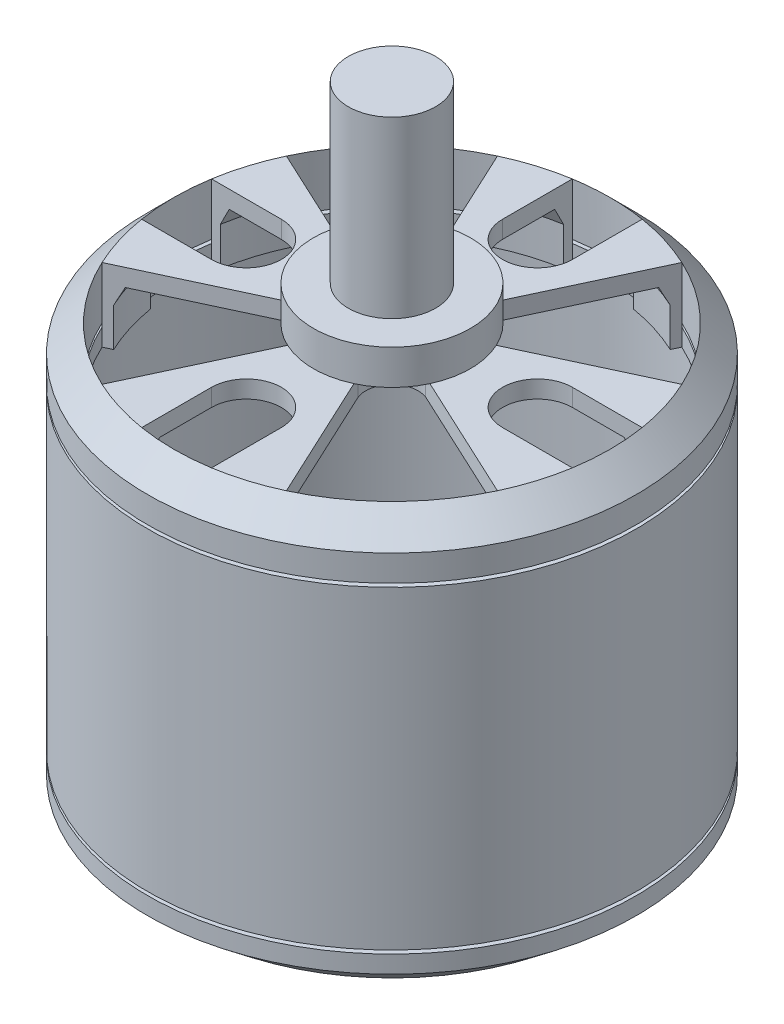
SolidWorks part; units mm, degrees
ref_plane "前视基准面" through (0, 0, 0) normal (0, 0, 1) x (1, 0, 0)
ref_plane "上视基准面" through (0, 0, 0) normal (0, 1, 0) x (1, 0, 0)
ref_plane "右视基准面" through (0, 0, 0) normal (1, 0, 0) x (0, 0, -1)
sketch "草图1" plane through (0, 0, 0) normal (1, 0, 0) x (0, 0, -1)
  line L0 (13.9995, 22.7) -> (12.5, 24.2)
  line L1 (12.5, 24.2) -> (4.5, 24.2)
  line L2 (4.5, 24.2) -> (4.5, 26.2)
  line L3 (13.9995, 22.7) -> (13.9995, 21.2)
  line L4 (13.9995, 21.2) -> (12.4995, 21.2)
  line L5 (12.4995, 21.2) -> (12.4995, 21)
  line L6 (12.4995, 21) -> (13.9995, 21)
  line L7 (13.9995, 3) -> (13.9995, 21)
  line L8 (1.5, 0.2) -> (12, 0.2)
  line L9 (14, 1.8) -> (14, 2.8)
  line L10 (14, 2.8) -> (10, 2.8)
  line L11 (10, 2.8) -> (10, 3)
  line L12 (11.9995, 22.2) -> (11.5, 23.2)
  line L13 (10, 3) -> (13.9995, 3)
  line L14 (0, 3) -> (4.2495, 3)
  line L15 (4.5, 26.2) -> (2.5, 26.2)
  line L17 (14, 1.8) -> (12, 0.2)
  line L18 (0, 23.2) -> (11.5, 23.2)
  line L19 (2.5, 26.2) -> (2.5, 36.2)
  line L20 (2.5, 36.2) -> (0, 36.2)
  line L21 (11.9995, 22.2) -> (11.9995, 20)
  line L22 (11.9995, 20) -> (12.9995, 20)
  line L23 (12.9995, 20) -> (12.9995, 4)
  line L24 (12.9995, 4) -> (4.2495, 4)
  line L25 (4.2495, 4) -> (4.2495, 3)
  line L26 (1.5, 0.2) -> (1.5, 0.5408)
  line L27 (1.5, 0.5408) -> (0.75, 0.5408)
  line L28 (0.75, 0.5408) -> (0.75, 0)
  line L29 (0.75, 0) -> (0, 0)
  line L30 (0, 36.2) -> (0, 23.2)
  line L31 (0, 0) -> (0, 3)
  line L32 (0, 0) -> (0, 9.9867) construction
  dimension "D22" = 0.5408
  dimension "D3" = 3
  dimension "D4" = 0.75
  dimension "D5" = 0.2
  dimension "D6" = 3.9995
  dimension "D7" = 1
  dimension "D8" = 1
  dimension "D9" = 1
  dimension "D10" = 2.5
  dimension "D11" = 4.5
  dimension "D12" = 4
  dimension "D13" = 1
  dimension "D14" = 1
  dimension "D15" = 1
  dimension "D16" = 1
  dimension "D17" = 0.2
  dimension "D18" = 24
  dimension "D19" = 1
  dimension "D20" = 1.5
  dimension "D21" = 1.4995
  dimension "D23" = 0.75
  dimension "D24" = 2
  dimension "D25" = 10
  dimension "D26" = 0.3408
  dimension "D27" = 3
  dimension "D28" = 1
  dimension "D29" = 4.2495
revolve "旋转2" add sketch "草图1" angle 360 about L32
ref_axis "基准轴1" through (0, -1.2249, 0) along (0, 1, 0)
sketch "草图2" plane through (0, 24.2, 0) normal (0, 1, 0) x (1, 0, 0)
  line L1 (-2, 12.339) -> (-2, 8.339)
  line L2 (2, 12.339) -> (2, 8.339)
  line L4 (-5.2827, 11.3288) -> (-1.6905, 3.6252)
  line L5 (-3.6252, 1.6905) -> (-11.3288, 5.2827)
  arc A1 (2, 12.339) -> (-2, 12.339) centre (0, 0) ccw
  arc A2 (-2, 8.339) -> (2, 8.339) centre (0, 8.339) ccw
  arc A3 (-5.2827, 11.3288) -> (-11.3288, 5.2827) centre (0, 0) ccw
  arc A4 (-3.6252, 1.6905) -> (-1.6905, 3.6252) centre (-3.0928, 3.0928) ccw
  dimension "D8" = 1.5
  dimension "D3" = 4
  dimension "D4" = 4
extrude "切除-拉伸1" cut sketch "草图2" against normal blind 10
ref_axis "基准轴3" through (0, -1.41, 0) along (0, 1, 0)
pattern_circular "阵列(圆周)1" count 4 over 360 about axis through (0, -1.41, 0) along (0, 1, 0) of "切除-拉伸1"
sketch "草图3" plane through (0, 0.2, 0) normal (0, -1, 0) x (1, 0, 0)
  circle A2 centre (8, 0) radius 3
  circle A3 centre (0, 8) radius 3
  circle A4 centre (-8, 0) radius 3
  circle A5 centre (0, -8) radius 3
  circle A7 centre (6.3333, 7.0809) radius 1.5
  circle A8 centre (-6.3333, -7.0809) radius 1.5
  circle A9 centre (-5.9628, 5.3333) radius 1.5
  circle A10 centre (5.9628, -5.3333) radius 1.5
  dimension "D2" = 6
  dimension "D3" = 6
  dimension "D4" = 6
  dimension "D6" = 3
  dimension "D7" = 3
  dimension "D8" = 3
extrude "切除-拉伸2" cut sketch "草图3" against normal blind 5
sketch "草图4" plane through (0, 36.2, 0) normal (0, 1, 0) x (1, 0, 0)
  circle A0 centre (0, 0) radius 2.5
  dimension "D1" = 5
